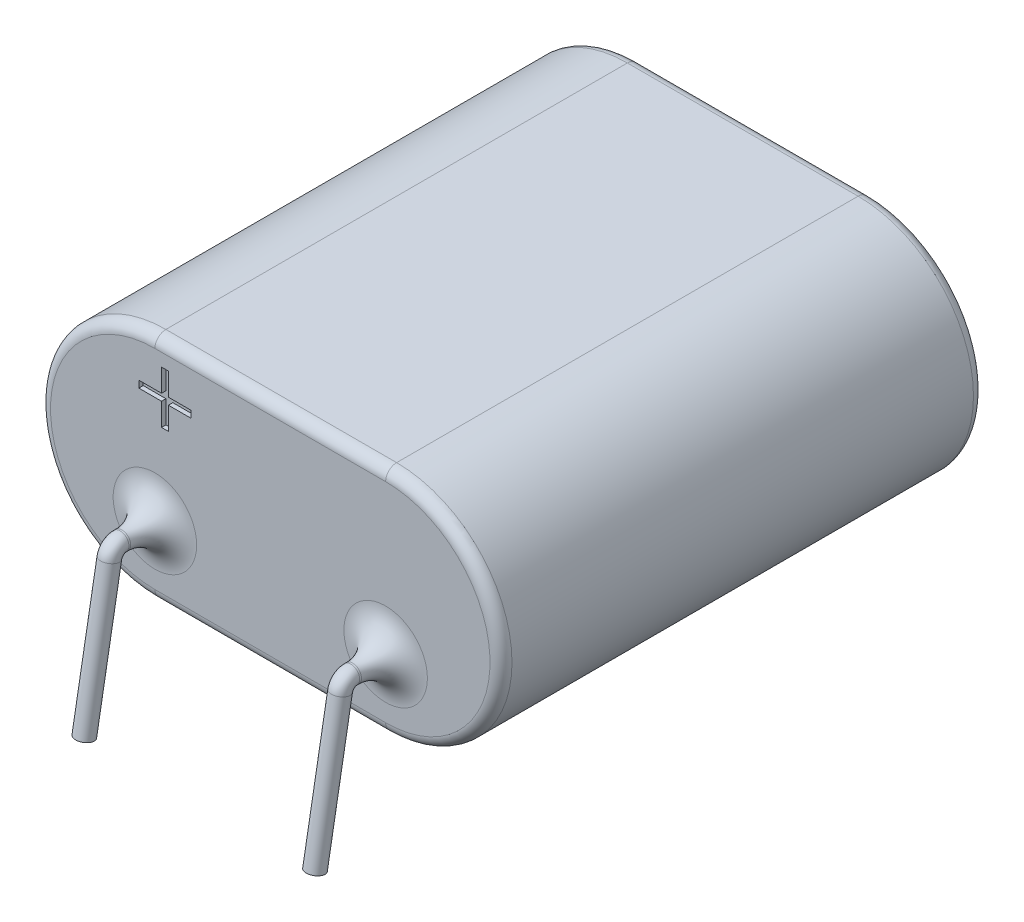
SolidWorks part; units mm, degrees
ref_plane "Front Plane" through (0, 0, 0) normal (0, 0, 1) x (1, 0, 0)
ref_plane "Top Plane" through (0, 0, 0) normal (0, 1, 0) x (1, 0, 0)
ref_plane "Right Plane" through (0, 0, 0) normal (1, 0, 0) x (0, 0, -1)
sketch "Sketch1" plane through (0, 0, 0) normal (0, 0, 1) x (1, 0, 0)
  line L0 (0, 5.25) -> (10.5, 5.25)
  line L1 (0, -5.25) -> (10.5, -5.25)
  arc A0 (0, 5.25) -> (0, -5.25) centre (0, 0) ccw
  arc A1 (10.5, -5.25) -> (10.5, 5.25) centre (10.5, 0) ccw
  dimension "D1" = 10.5
  dimension "D2" = 10.5
extrude "Boss-Extrude1" add sketch "Sketch1" against normal blind 22
sketch "Sketch2" plane through (0, 0, 0) normal (0, 0, 1) x (1, 0, 0)
  line L0 (0, 0) -> (0, 50000) construction
  line L1 (10.5, 0) -> (10.5, 50000) construction
  line L2 (0, -5.25) -> (10.5, -5.25) construction
  arc A0 (10.5, -5.25) -> (10.5, 5.25) centre (10.5, 0) ccw construction
  arc A1 (10.5, -5.25) -> (10.5, 5.25) centre (10.5, 0) ccw construction
  circle A2 centre (0, -2.05) radius 0.4
  circle A3 centre (10.5, -2.05) radius 0.4
  dimension "D1" = 0.8
  dimension "D2" = 3.2
ref_point "Point1"
ref_point "Point2"
ref_axis "Axis1" through (0, 0, 0) along (0, 1, 0)
ref_plane "Plane1" through (0, 0, 0) normal (1, 0, 0) x (0, 1, 0)
sketch "Sketch3" plane through (0, 0, 0) normal (1, 0, 0) x (0, 1, 0)
  line L0 (-2.05, 0) -> (-2.05, 1.5805)
  line L1 (-2.4632, 2.0729) -> (-8.9437, 3.2155)
  arc A0 (-2.05, 1.5805) -> (-2.4632, 2.0729) centre (-2.55, 1.5805) ccw
  point P6 (-2.05, 2)
  dimension "D3" = 0.5
  dimension "D1" = 2
  dimension "D2" = 7
  dimension "D4" = 100
sweep "Sweep1" add profiles "Sketch2" path "Sketch3"
fillet "Fillet1" radius 1.5 2 edges at (10.9, -2.05, 0) (0.4, -2.05, 0)
fillet "Fillet2" radius 0.5 8 edges at (5.25, -5.25, -22) (15.75, 0, -22) (5.25, 5.25, -22) (-5.25, 0, -22) (5.25, 5.25, 0) (15.75, 0, 0) (5.25, -5.25, 0) (-5.25, 0, 0)
sketch "Sketch4" plane through (0, 0, 0) normal (0, 0, 1) x (1, 0, 0)
  line L1 (-1, 1.25) -> (3, 1.25) construction
  line L2 (0, 5.25) -> (10.5, 5.25) construction
  line L5 (0, -11) -> (0, 11) construction
  text T0 "+\r\n"
  dimension "D1" = 4
  dimension "D2" = 4
  dimension "D3" = 1
extrude "Cut-Extrude1" cut sketch "Sketch4" against normal blind 0.2
